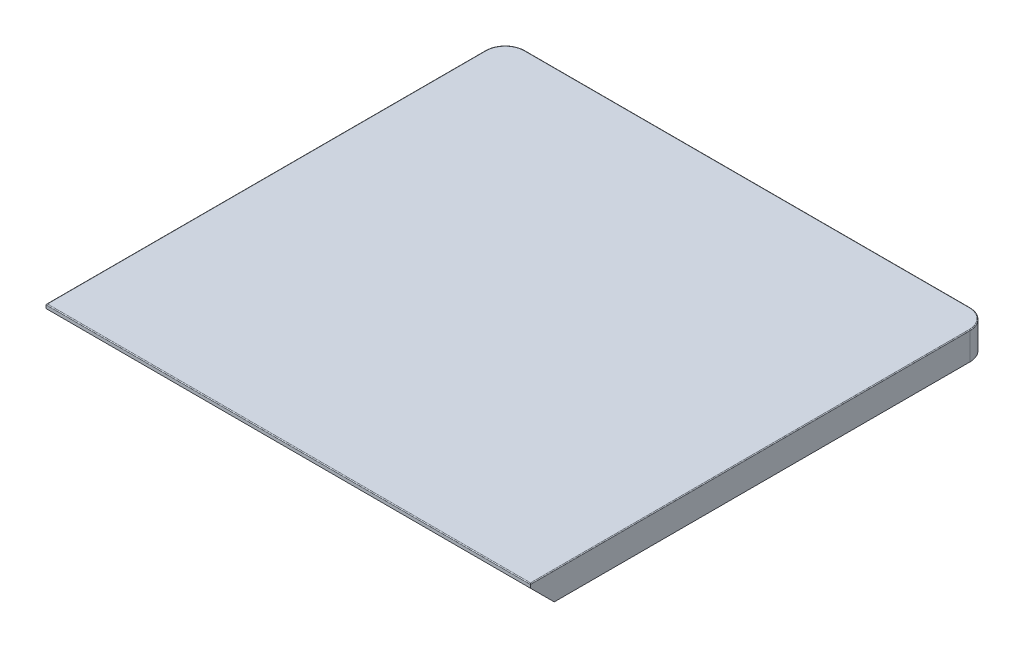
SolidWorks part; units mm, degrees
other "Markup1"
sketch "Sketch2" plane through (-497.2926, 35, -260) normal (0, 1, 0) x (1, 0, 0)
material "Alloy Steel (SS)"
ref_plane "Front Plane" through (0, 0, 0) normal (0, 0, 1) x (1, 0, 0)
ref_plane "Top Plane" through (0, 0, 0) normal (0, 1, 0) x (1, 0, 0)
ref_plane "Right Plane" through (0, 0, 0) normal (1, 0, 0) x (0, 0, -1)
sketch "Sketch1" plane through (0, 0, 0) normal (0, 1, 0) x (1, 0, 0)
  line L1 (114.7074, -320) -> (-497.2926, -320)
  line L2 (114.7074, -320) -> (114.7074, 260)
  line L3 (114.7074, 260) -> (-497.2926, 260)
  line L4 (-497.2926, -320) -> (-497.2926, 260)
  line L5 (114.7074, -320) -> (-497.2926, 260) construction
  line L6 (114.7074, 260) -> (-497.2926, -320) construction
  point P0 (0, 0)
  dimension "D1" = 580
  dimension "D2" = 612
extrude "Boss-Extrude1" add sketch "Sketch1" along normal blind 35
fillet "Fillet9" radius 1 4 edges at (-191.2926, 35, -260) (114.7074, 35, 30) (-191.2926, 35, 320) (-497.2926, 35, 30)
chamfer "Chamfer1" distance 30 1 edges at (-191.2926, 0, 320) tangent propagation no
fillet "Fillet10" radius 25 4 edges at (114.4145, 34.7071, -259.7071) (-496.9997, 34.7071, -259.7071) (-497.2926, 17, -260) (114.7074, 17, -260)
sketch "Sketch3" plane through (0, 0, 0) normal (0, -1, 0) x (1, 0, 0)
  line L0 (-497.2926, -235) -> (-497.2926, 290) construction
  line L1 (19.7759, -225.4965) -> (-18.1502, -225.4965)
  line L2 (19.7759, -225.4965) -> (19.7759, 229.5035)
  line L3 (19.7759, 229.5035) -> (-18.1502, 229.5035)
  line L4 (-18.1502, -225.4965) -> (-18.1502, 229.5035)
  line L5 (19.7759, -225.4965) -> (-18.1502, 229.5035) construction
  line L6 (19.7759, 229.5035) -> (-18.1502, -225.4965) construction
  line L7 (-362.2926, -224.8479) -> (-402.2926, -225.6034)
  line L8 (-362.2926, -224.8479) -> (-362.2926, 229.3966)
  line L9 (-362.2926, 229.3966) -> (-402.2926, 229.3966)
  line L10 (-402.2926, -225.6034) -> (-402.2926, 229.3966)
  line L11 (-362.2926, -224.8479) -> (-402.2926, 229.3966) construction
  line L12 (-362.2926, 229.3966) -> (-402.2926, -225.6034) construction
  line L13 (-18.1502, -225.4965) -> (-417.2719, -225.4965) construction
  line L14 (-18.1502, 229.5035) -> (-417.2719, 229.5035) construction
  line L15 (19.7759, 0) -> (114.7759, 0) construction
  point P0 (0, 0)
  point P5 (-417.2719, 0)
  dimension "D1" = 40
  dimension "D2" = 455
  dimension "D3" = 37.9261
  dimension "D4" = 455
  dimension "D5" = 95
  dimension "D6" = 95
extrude "Boss-Extrude2" add sketch "Sketch3" along normal blind 35
chamfer "Chamfer2" distance 50 4 edges at (0.8129, -35, -225.4965) (-382.2926, -35, -225.2256) (-382.2926, -35, 229.3966) (0.8129, -35, 229.5035)
sketch "Sketch4" plane through (0, -35, 0) normal (0, -1, 0) x (1, 0, 0)
  line L0 (-6.7699, 179.5035) -> (-6.7699, -175.4965)
  line L1 (5.4232, 179.5035) -> (5.4232, -175.4965)
  line L2 (-390.447, 179.3966) -> (-390.447, -175.3707)
  line L3 (-375.8152, 179.3966) -> (-375.8152, -175.0944)
  line L4 (-390.447, 179.3966) -> (-375.8152, 179.3966)
  line L5 (-390.447, -175.3707) -> (-375.8152, -175.0944)
  line L6 (-6.7699, -175.4965) -> (5.4232, -175.4965)
  line L7 (-6.7699, 179.5035) -> (5.4232, 179.5035)
extrude "Cut-Extrude1" cut sketch "Sketch4" against normal blind 20
